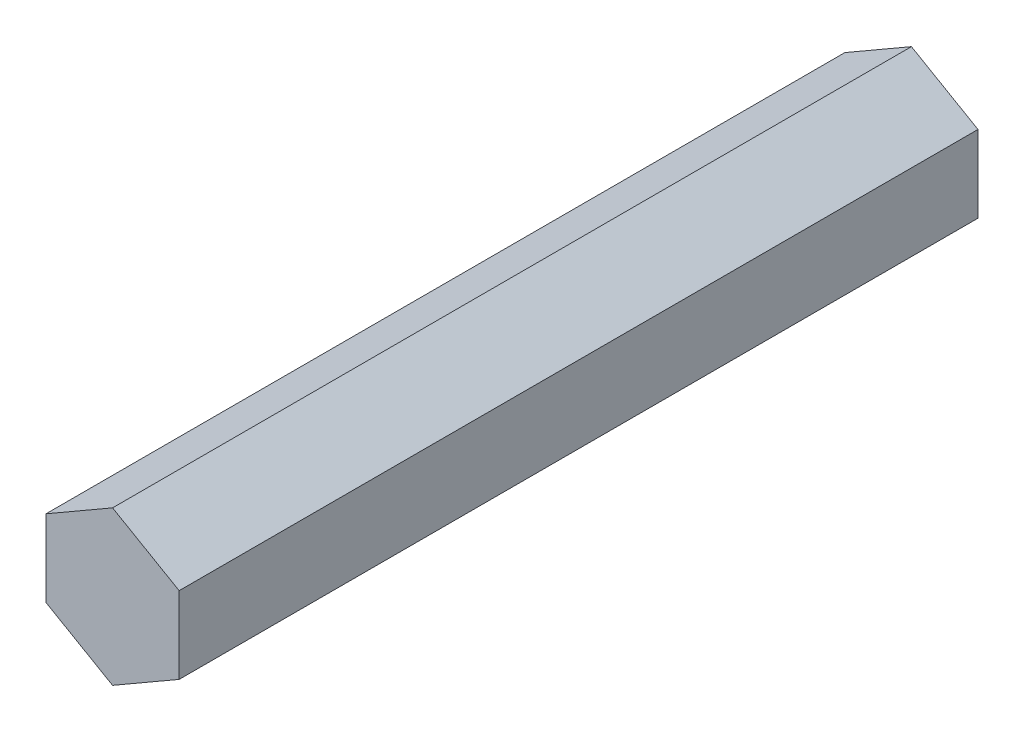
SolidWorks part; units mm, degrees
ref_plane "Piano frontale" through (0, 0, 0) normal (0, 0, 1) x (1, 0, 0)
ref_plane "Piano superiore" through (0, 0, 0) normal (0, 1, 0) x (1, 0, 0)
ref_plane "Piano destro" through (0, 0, 0) normal (1, 0, 0) x (0, 0, -1)
sketch "Schizzo1" plane through (0, 0, 0) normal (0, 0, 1) x (1, 0, 0)
  line L1 (0, -16.9648) -> (-2.5, -18.4081)
  line L2 (-2.5, -18.4081) -> (-2.5, -21.2949)
  line L3 (-2.5, -21.2949) -> (0, -22.7383)
  line L4 (0, -22.7383) -> (2.5, -21.2949)
  line L5 (2.5, -21.2949) -> (2.5, -18.4081)
  line L6 (2.5, -18.4081) -> (0, -16.9648)
  circle A0 centre (0, -19.8515) radius 2.5 construction
extrude "Estrusione-Estrusione1" add sketch "Schizzo1" along normal blind 30
